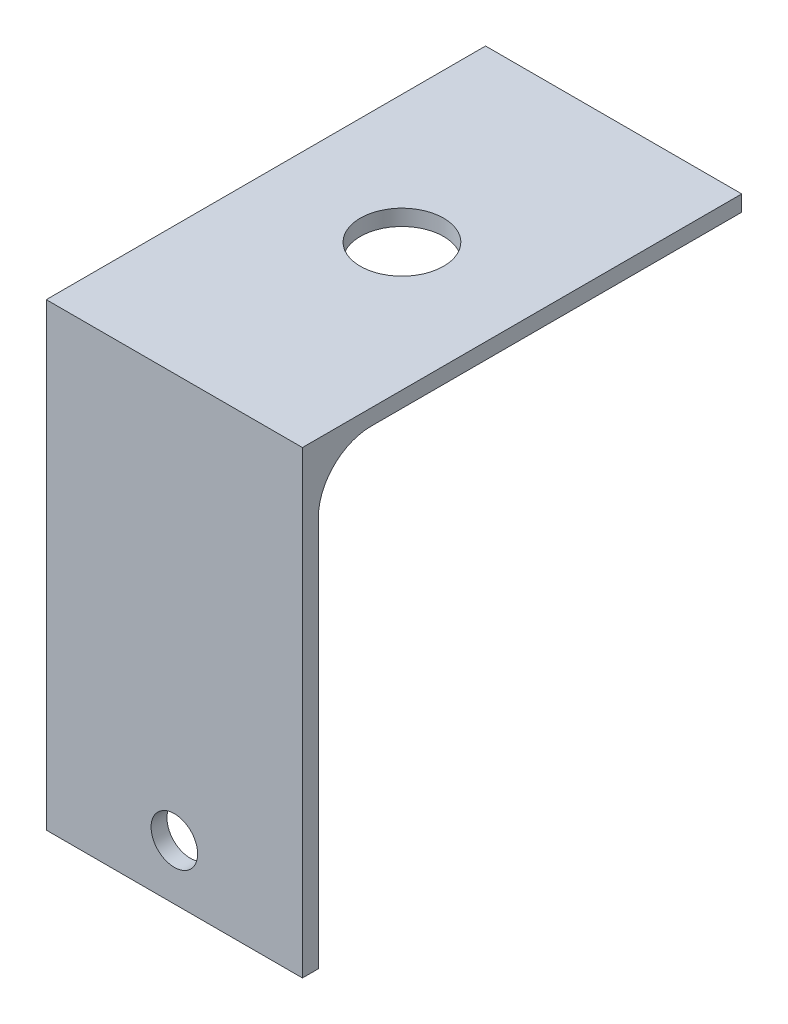
SolidWorks part; units mm, degrees
material "1060 Alloy"
ref_plane "Front Plane" through (0, 0, 0) normal (0, 0, 1) x (1, 0, 0)
ref_plane "Top Plane" through (0, 0, 0) normal (0, 1, 0) x (1, 0, 0)
ref_plane "Right Plane" through (0, 0, 0) normal (1, 0, 0) x (0, 0, -1)
sketch "Sketch1" plane through (0, 0, 0) normal (0, 0, 1) x (1, 0, 0)
  line L1 (12.1, -21.7) -> (-12.1, -21.7)
  line L2 (12.1, -21.7) -> (12.1, 21.7)
  line L3 (12.1, 21.7) -> (-12.1, 21.7)
  line L4 (-12.1, -21.7) -> (-12.1, 21.7)
  line L5 (12.1, -21.7) -> (-12.1, 21.7) construction
  line L6 (12.1, 21.7) -> (-12.1, -21.7) construction
  point P0 (0, 0)
  dimension "Base" = 24.2
  dimension "ServoToTop" = 43.4
extrude "Boss-Extrude1" add sketch "Sketch1" along normal blind 1.5
sketch "Sketch2" plane through (0, 0, 1.5) normal (0, 0, 1) x (1, 0, 0)
  line L0 (-12.1, -21.7) -> (12.1, -21.7) construction
  line L1 (12.1, -21.7) -> (12.1, 21.7) construction
  circle A0 centre (0, -16.5) radius 2.2
  dimension "D2" = 4.4
  dimension "D1" = 5.2
  dimension "D3" = 12.1
extrude "Cut-Extrude1" cut sketch "Sketch2" against normal through all
sketch "Sketch4" plane through (0, 21.7, 0) normal (0, 1, 0) x (1, 0, 0)
  line L0 (-12.1, -1.5) -> (-12.1, 0) construction
  line L1 (-12.1, 0) -> (12.1, 0)
  line L2 (-12.1, 0) -> (-12.1, 40)
  line L3 (-12.1, 40) -> (12.1, 40)
  line L4 (12.1, 0) -> (12.1, 40)
  line L5 (12.1, -1.5) -> (12.1, 0) construction
  dimension "BaseTopLength" = 40
extrude "Boss-Extrude2" add sketch "Sketch4" against normal blind 1.5
sketch "Sketch5" plane through (0, 20.2, 0) normal (0, -1, 0) x (1, 0, 0)
  line L0 (-12.1, 0) -> (12.1, 0) construction
  line L1 (-12.1, -40) -> (-12.1, 0) construction
  circle A0 centre (0, -20) radius 3.937
  dimension "D1" = 7.874
  dimension "D2" = 20
  dimension "D3" = 12.1
extrude "Cut-Extrude2" cut sketch "Sketch5" against normal through all
fillet "Fillet1" radius 5 1 edges at (0, 20.2, 0) type face fillet first side face at (0, 20.2, -23.937) second side face at (2.2, -16.5, 0)
